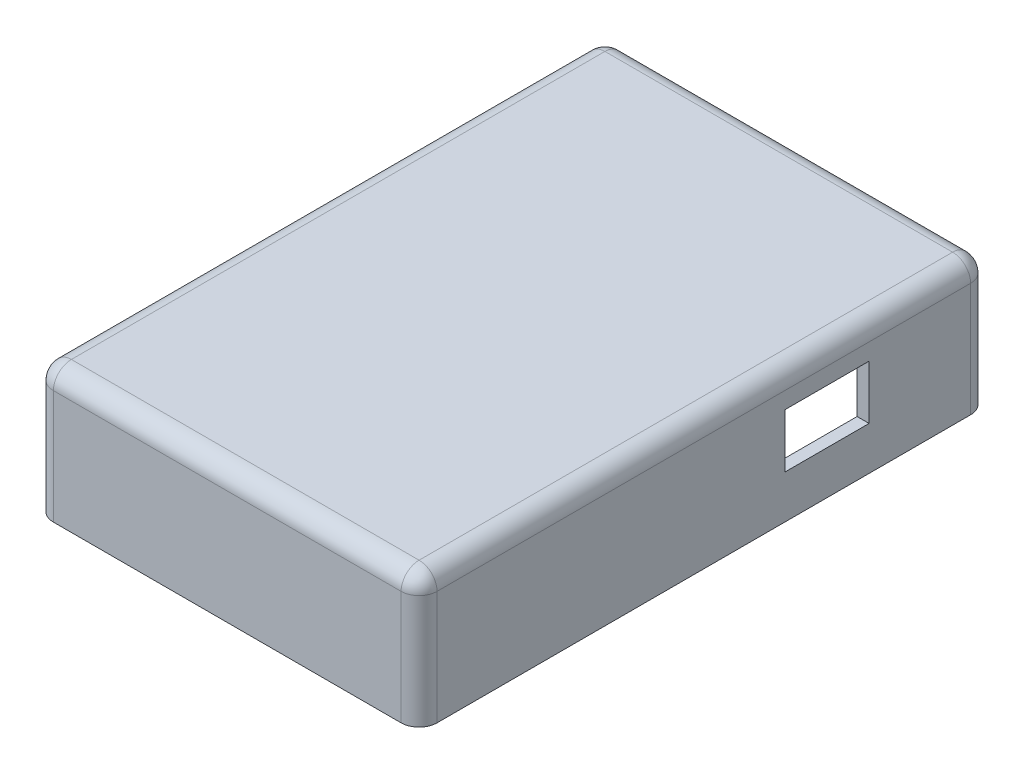
SolidWorks part; units mm, degrees
ref_plane "Front Plane" through (0, 0, 0) normal (0, 0, 1) x (1, 0, 0)
ref_plane "Top Plane" through (0, 0, 0) normal (0, 1, 0) x (1, 0, 0)
ref_plane "Right Plane" through (0, 0, 0) normal (1, 0, 0) x (0, 0, -1)
sketch "Sketch1" plane through (0, 0, 0) normal (0, 1, 0) x (1, 0, 0)
  line L5 (-32, -47.5) -> (32, -47.5)
  line L6 (-32, -47.5) -> (-32, 47.5)
  line L7 (-32, 47.5) -> (32, 47.5)
  line L8 (32, -47.5) -> (32, 47.5)
  line L9 (-32, -47.5) -> (32, 47.5) construction
  line L10 (-32, 47.5) -> (32, -47.5) construction
  point P0 (0, 0)
  dimension "D1" = 64
  dimension "D2" = 95
extrude "Boss-Extrude1" add sketch "Sketch1" along normal blind 2
sketch3d "3DSketch3"
  line L0 (-30, 0, 45.5) -> (-30, 0, -45.5)
  line L1 (-30, 0, -45.5) -> (30, 0, -45.5)
  line L2 (30, 0, -45.5) -> (30, 0, 45.5)
  line L3 (30, 0, 45.5) -> (-30, 0, 45.5)
  line L4 (-30, 0, 45.5) -> (-30, 0, -45.5)
  line L5 (-30, 0, -45.5) -> (30, 0, -45.5)
  line L6 (30, 0, -45.5) -> (30, 0, 45.5)
  line L7 (30, 0, 45.5) -> (-30, 0, 45.5)
  line L9 (-32, 0, 47.5) -> (-32, 0, -47.5)
  line L10 (-32, 0, 47.5) -> (32, 0, 47.5)
  line L11 (32, 0, 47.5) -> (32, 0, -47.5)
  line L12 (-32, 0, -47.5) -> (32, 0, -47.5)
  dimension "D1" = 2
extrude "Boss-Extrude2" add sketch "3DSketch3" along direction (0, -1, 0) on the side against the normal blind 20 contours L10 L9 L12 L11 | L4 L5 L6 L7
sketch "Sketch2" plane through (0, -20, 0) normal (0, -1, 0) x (1, 0, 0)
  line L8 (31, 46.5) -> (-31, 46.5)
  line L9 (-31, 46.5) -> (-31, -46.5)
  line L10 (-31, -46.5) -> (31, -46.5)
  line L11 (31, -46.5) -> (31, 46.5)
  line L12 (31, 46.5) -> (-31, 46.5)
  line L13 (-31, 46.5) -> (-31, -46.5)
  line L14 (-31, -46.5) -> (31, -46.5)
  line L15 (31, -46.5) -> (31, 46.5)
  dimension "D1" = 1
extrude "Cut-Extrude1" cut sketch "Sketch2" against normal blind 1.5
fillet "Fillet1" radius 10 4 edges
sketch "Sketch3" plane through (0, 0, 0) normal (0, -1, 0) x (1, 0, 0)
  line L5 (-26.5, 24.5) -> (26.5, -4.5) construction
  line L6 (-26.5, -4.5) -> (26.5, 24.5) construction
  circle A0 centre (-26.5, 24.5) radius 3
  circle A1 centre (26.5, 24.5) radius 3
  circle A2 centre (26.5, -4.5) radius 3
  circle A3 centre (-26.5, -4.5) radius 3
  circle A4 centre (-26.5, 24.5) radius 1.25
  circle A5 centre (26.5, 24.5) radius 1.25
  circle A6 centre (26.5, -4.5) radius 1.25
  circle A7 centre (-26.5, -4.5) radius 1.25
  point P0 (0, 10)
  dimension "D1" = 53
  dimension "D2" = 29
  dimension "D3" = 10
extrude "Boss-Extrude3" add sketch "Sketch3" along normal blind 3
sketch "Sketch9" plane through (-32, 0, 0) normal (-1, 0, 0) x (0, 0, 1)
  line L0 (14.7349, -20) -> (14.7349, -18.2228)
  line L1 (47.5, -20) -> (-47.5, -20) construction
  line L2 (13.102, -16.59) -> (7.992, -16.59)
  line L3 (6.2349, -18.3471) -> (6.2349, -20)
  line L4 (6.2349, -20) -> (14.7349, -20)
  line L5 (14.2349, -18.94) -> (14.2349, -18.34) construction
  line L6 (6.7349, -18.94) -> (6.7349, -18.34) construction
  line L7 (10.4949, -17.09) -> (12.9849, -17.09) construction
  line L8 (14.442, -17.5157) -> (13.8091, -16.8829)
  line L9 (6.5278, -17.64) -> (7.2849, -16.8829)
  line L10 (14.0738, -17.8546) -> (13.4702, -17.2511) construction
  line L12 (14.4349, -18.0926) -> (14.4349, -17.3817) construction
  arc A0 (13.8091, -16.8829) -> (13.102, -16.59) centre (13.102, -17.59) ccw
  arc A1 (14.442, -17.5157) -> (14.7349, -18.2228) centre (13.7349, -18.2228) cw
  arc A2 (6.5278, -17.64) -> (6.2349, -18.3471) centre (7.2349, -18.3471) ccw
  arc A3 (7.2849, -16.8829) -> (7.992, -16.59) centre (7.992, -17.59) cw
  point P20 (14.4349, -17.5086)
  dimension "D5" = 1
  dimension "D1" = 0.5
  dimension "D2" = 0.5
  dimension "D3" = 0.5
  dimension "D4" = 0.5
extrude "Cut-Extrude3" cut sketch "Sketch9" against normal up to next
sketch "Sketch10" plane through (-32, 0, 0) normal (-1, 0, 0) x (0, 0, 1)
  circle A0 centre (1.2, -10) radius 1.5
extrude "Cut-Extrude4" cut sketch "Sketch10" against normal up to next
sketch "Sketch11" plane through (0, 0, -47.5) normal (0, 0, -1) x (-1, 0, 0)
  line L0 (32, -20) -> (-32, -20) construction
  circle A0 centre (0, -20) radius 4
extrude "Cut-Extrude5" cut sketch "Sketch11" against normal up to next
sketch "Sketch13" plane through (0, 0, 0) normal (0, -1, 0) x (1, 0, 0)
  line L0 (30, -35.5) -> (30, 35.5) construction
  line L1 (15.25, -43.07) -> (-25.25, -43.07)
  line L2 (15.25, -43.07) -> (15.25, -34.57)
  line L3 (15.25, -34.57) -> (-25.25, -34.57)
  line L4 (-25.25, -43.07) -> (-25.25, -34.57)
  line L5 (-20, -45.5) -> (20, -45.5) construction
  line L6 (12.75, -40.57) -> (12.75, -37.07)
  line L7 (12.75, -37.07) -> (-22.75, -37.07)
  line L8 (-22.75, -40.57) -> (-22.75, -37.07)
  line L9 (12.75, -40.57) -> (-22.75, -40.57)
  dimension "D1" = 14.75
  dimension "D2" = 2.43
  dimension "D3" = 40.5
  dimension "D4" = 8.5
  dimension "D5" = 2.5
extrude "Boss-Extrude4" add sketch "Sketch13" along normal blind 20
sketch "Sketch15" plane through (0, 0, 0) normal (0, -1, 0) x (1, 0, 0)
  line L1 (-22.75, -37.07) -> (12.75, -37.07)
  line L2 (-22.75, -37.07) -> (-22.75, -40.57)
  line L3 (-22.75, -40.57) -> (12.75, -40.57)
  line L4 (12.75, -37.07) -> (12.75, -40.57)
extrude "Boss-Extrude5" add sketch "Sketch15" along normal blind 11
sketch "Sketch17" plane through (0, 0, -34.57) normal (0, 0, 1) x (1, 0, 0)
  line L0 (15.25, -20) -> (-25.25, -20) construction
  line L1 (4.75, -20) -> (-15.25, -20)
  line L2 (4.75, -20) -> (4.75, -15.5)
  line L3 (4.75, -15.5) -> (-15.25, -15.5)
  line L4 (-15.25, -20) -> (-15.25, -15.5)
  line L5 (15.25, -20) -> (15.25, 0) construction
  dimension "D1" = 4.5
  dimension "D2" = 20
  dimension "D3" = 10.5
extrude "Cut-Extrude6" cut sketch "Sketch17" against normal blind 9
chamfer "Chamfer4" distance 4.2 angle 45 1 edges at (-15.25, -20, -35.82)
sketch "Sketch18" plane through (0, 0, 0) normal (0, -1, 0) x (1, 0, 0)
  line L6 (-31, 46.5) -> (-16, 31.5) construction
  line L11 (16, -31.5) -> (31, -46.5) construction
  circle A1 centre (-25.6575, 41.1575) radius 1.25
  circle A2 centre (25.6575, -41.1575) radius 5
  circle A3 centre (25.6575, -41.1575) radius 1.25
  circle A6 centre (-25.6575, 41.1575) radius 5
  point P0 (0, 0)
  dimension "D1" = 21.9203
  dimension "D5" = 48.5
  dimension "D6" = 48.5
extrude "Boss-Extrude6" add sketch "Sketch18" along normal up to surface (18.5 mm away) up to face at (2.2683, -18.5, 5.157)
sketch "Sketch19" plane through (32, 0, 0) normal (1, 0, 0) x (0, 0, -1)
  line L1 (27.565, -12.7766) -> (13.565, -12.7766)
  line L2 (27.565, -12.7766) -> (27.565, -3.7766)
  line L3 (27.565, -3.7766) -> (13.565, -3.7766)
  line L4 (13.565, -12.7766) -> (13.565, -3.7766)
  line L5 (27.565, -12.7766) -> (13.565, -3.7766) construction
  line L6 (27.565, -3.7766) -> (13.565, -12.7766) construction
  point P0 (20.565, -8.2766)
  dimension "D1" = 14
  dimension "D2" = 9
extrude "Cut-Extrude7" cut sketch "Sketch19" against normal up to next
fillet "Fillet2" radius 3 4 edges
fillet "Fillet3" radius 3 8 edges at (-32, 2, 0) (-31.1213, 2, -46.6213) (0, 2, -47.5) (31.1213, 2, -46.6213) (32, 2, 0) (31.1213, 2, 46.6213) (0, 2, 47.5) (-31.1213, 2, 46.6213)
sketch "Sketch20" plane through (0, 0, 0) normal (0, -1, 0) x (1, 0, 0)
  line L0 (4.75, -43.07) -> (15.25, -43.07) construction
  line L1 (10, -43.07) -> (13, -43.07)
  line L2 (10, -43.07) -> (10, -45.5)
  line L3 (10, -45.5) -> (13, -45.5)
  line L4 (13, -43.07) -> (13, -45.5)
  line L5 (20, -45.5) -> (3.7081, -45.5) construction
  line L6 (-25.25, -43.07) -> (-15.25, -43.07) construction
  line L7 (-20.25, -43.07) -> (-17.25, -43.07)
  line L8 (-20.25, -43.07) -> (-20.25, -45.5)
  line L9 (-20.25, -45.5) -> (-17.25, -45.5)
  line L10 (-17.25, -43.07) -> (-17.25, -45.5)
  line L11 (-3.7081, -45.5) -> (-20, -45.5) construction
  dimension "D1" = 3
  dimension "D2" = 3
extrude "Boss-Extrude7" add sketch "Sketch20" along normal up to surface (18.5 mm away) up to face at (-21.641, -18.5, -29.8716)
fillet "Fillet6" radius 1 4 edges at (-20.25, -9.25, -43.07) (10, -9.25, -43.07) (13, -9.25, -43.07) (-17.25, -9.25, -43.07)
fillet "Fillet7" radius 2 3 edges at (-25.25, 0, -38.82) (15.25, 0, -38.82) (-5, 0, -34.57)
